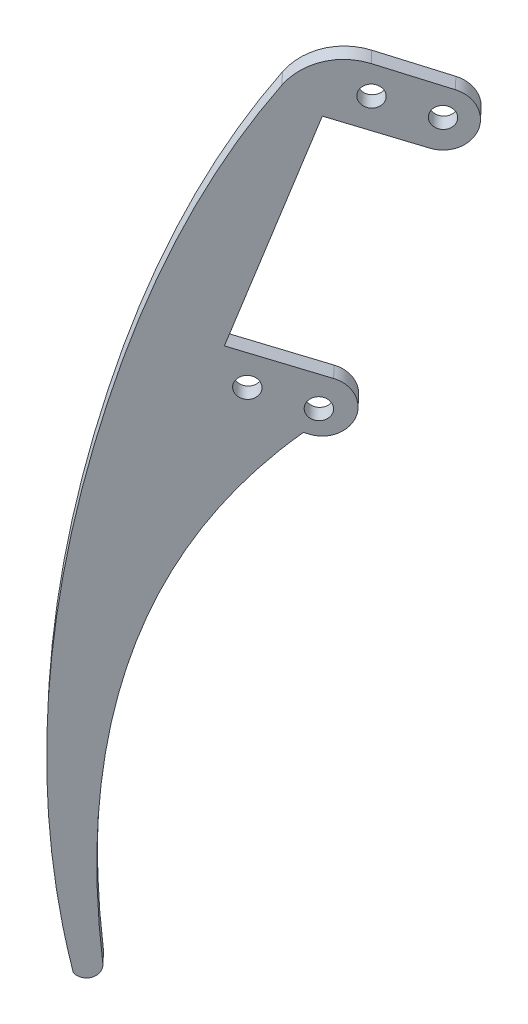
SolidWorks part; units mm, degrees
material "1345 Alloy"
ref_plane "Front Plane" through (0, 0, 0) normal (0, 0, 1) x (1, 0, 0)
ref_plane "Top Plane" through (0, 0, 0) normal (0, 1, 0) x (1, 0, 0)
ref_plane "Right Plane" through (0, 0, 0) normal (1, 0, 0) x (0, 0, -1)
ref_plane "Plane1" through (-18.7474, 0, -19.7975) normal (0.6876, 0, 0.7261) x (0, 1, 0)
sketch "Sketch1" plane through (-18.7474, 0, -19.7975) normal (0.6876, 0, 0.7261) x (0, 1, 0)
  line L0 (47.1347, 186.5931) -> (102.0294, 167.6057)
  line L1 (48.9616, 191.8751) -> (47.1347, 186.5931)
  line L2 (102.0294, 167.6057) -> (110.1178, 189.9999)
  arc A0 (-37.3051, 221.68) -> (-35.7838, 217.8531) centre (-35.9409, 220.0065) ccw
  ellipse E1 centre (-821.1483, -833.3328) end of major axis (-1683.345, -1866.2447) minor radius 311.0675 (48.9616, 191.8751) -> (-35.7838, 217.8531) ccw
  spline S0 degree 3 poles (110.1178, 189.9999) (95.5568, 201.9583) (77.204, 210.1732) (27.9425, 224.856) (-5.5514, 228.3479) (-37.3051, 221.68) knots 0.208168 0.208168 0.208168 0.208168 0.5 0.5 1 1 1 1
  point P3 (140.7948, 92.5972)
  point P4 (142.2455, 141.4622)
  point P5 (110.1178, 189.9999)
  point P6 (102.0294, 167.6057)
  point P7 (118.9604, 175.1388)
  point P8 (130.5785, 94.5232)
  point P18 (-821.1483, -833.3328)
  point P19 (-1683.345, -1866.2447)
  point P20 (-582.3431, -1032.6694)
  point P21 (48.9616, 191.8751)
  point P22 (-35.7838, 217.8531)
  point P23 (9.8812, 215.1476)
  point P24 (-1652.1779, -1881.8132)
extrude "Boss-Extrude1" add sketch "Sketch1" against normal blind 3
sketch "Sketch2" plane through (-20.8102, 0, -21.9758) normal (-0.6876, 0, -0.7261) x (-0.7261, 0, 0.6876)
  line L0 (170.8221, 92.7306) -> (183.5089, 56.0516)
  line L1 (183.5089, 56.0516) -> (202.1125, 62.4863)
  line L2 (202.1125, 62.4863) -> (189.4257, 99.1654)
  line L3 (189.4257, 99.1654) -> (170.8221, 92.7306)
extrude "Cut-Extrude1" cut sketch "Sketch2" against normal through all
hole_wizard "M3.5 Clearance Hole1" positions "Sketch4" profile "Sketch3" hole size "M3.5" standard "ANSI Metric"
sketch "Sketch4" plane through (-18.7474, 0, -19.7975) normal (0.6876, 0, 0.7261) x (0.7261, 0, -0.6876)
  point P0 (-183.0588, 102.4594)
  point P1 (-199.1415, 55.9624)
  point P2 (-189.8757, 52.7575)
  point P3 (-173.793, 99.2545)
sketch "Sketch3" plane through (-151.6665, 102.4594, 106.0717) normal (0, 1, 0) x (0.7261, 0, -0.6876)
  line L0 (0, 0) -> (0, 33.326)
  line L1 (0, 33.326) -> (1.905, 33.326)
  line L2 (1.905, 33.326) -> (1.905, 0)
  line L5 (1.905, 0) -> (0, 0)
  line L11 (0, -6.35) -> (0, 107.95) construction
  dimension "Thru Hole Dia." = 3.81
  dimension "Thru Hole Depth" = 33.326
fillet "Fillet3" radius 10 1 edges at (-157.7379, 110.1178, 109.7551) type face fillet first side face at (-163.4886, 73.2621, 115.2009) second side face at (-149.6076, 106.0736, 102.0561)
fillet "Fillet4" 2 edges at (-141.4774, 102.0294, 94.3572) (-143.8128, 92.7306, 96.5687) type full round first side face at (-147.1024, 104.8275, 99.6838) second side face at (-150.5668, 95.948, 102.9645) middle face at (-142.6451, 97.38, 95.4629)
fillet "Fillet10" 2 edges at (-153.0247, 56.0516, 105.292) (-155.2642, 47.1347, 107.4127) type full round first side face at (-159.7788, 59.2689, 111.6878) second side face at (-157.1818, 48.0482, 109.2286) middle face at (-154.1444, 51.5931, 106.3523)
